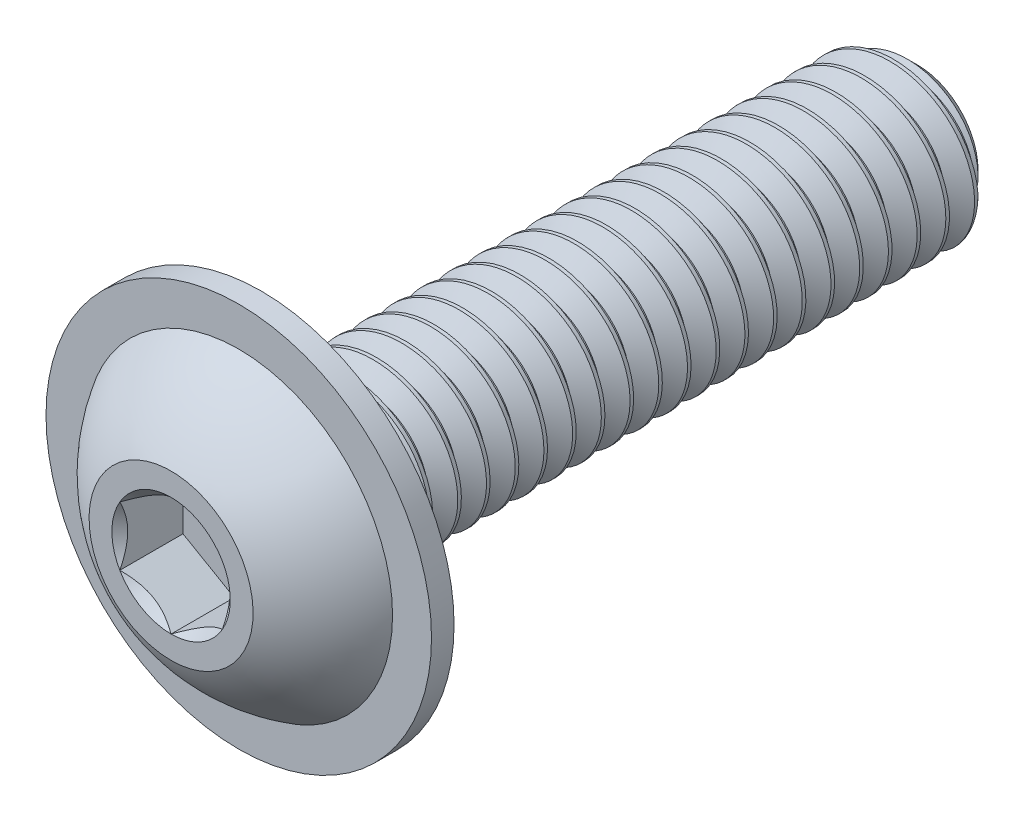
SolidWorks part; units mm, degrees
ref_plane "Front" through (0, 0, 0) normal (0, 0, 1) x (1, 0, 0)
ref_plane "Top" through (0, 0, 0) normal (0, 1, 0) x (1, 0, 0)
ref_plane "Right" through (0, 0, 0) normal (1, 0, 0) x (0, 0, -1)
sketch "Sketch1" plane through (0, 0, 0) normal (1, 0, 0) x (0, 0, -1)
  line L2 (2.2, 2) -> (18.2, 2)
  line L3 (18.2, 2) -> (18.2, 0)
  line L4 (18.2, 0) -> (2.2, 0)
  line L6 (1.65, 3.75) -> (2.2, 3.75) construction
  line L7 (18.2, 2) -> (18.2, -2) construction
  line L8 (0, 0) -> (2.2, 0) construction
  line L9 (2.2, 3.75) -> (2.2, -3.75) construction
  line L11 (2.2, 2) -> (2.2, 0)
  line L13 (0, 1.25) -> (0, -1.25) construction
  line L14 (0, 1.25) -> (0, 2) construction
  line L15 (1.65, 3.75) -> (1.65, 4.7) construction
  line L16 (1.65, 4.7) -> (2.2, 4.7) construction
  line L17 (2.2, 4.7) -> (2.2, 3.75) construction
  line L18 (2.2, 4.7) -> (2.2, -4.7) construction
  arc A3 (0, 2) -> (1.65, 3.75) centre (3.8742, 0) cw construction
  dimension "D1" = 0.55
revolve "Revolve1" add sketch "Sketch1" angle 360 mid plane about L4
sketch "Sketch3" plane through (0, 0, -18.2) normal (0, 0, -1) x (-1, 0, 0)
  circle A0 centre (0, 0) radius 2
curve "Helix/Spiral1" pitch 0.7 height 16.7 radius 2 centre (0, 0, -18.2) axis (0, 0, 1) start towards (0, 1, 0)
sketch "Sketch2" plane through (0, 0, 0) normal (1, 0, 0) x (0, 0, -1)
  line L0 (18.2, 2) -> (18.8125, 2)
  line L1 (18.8125, 2) -> (18.55, 1.5453)
  line L2 (18.55, 1.5453) -> (18.4625, 1.5453)
  line L3 (18.4625, 1.5453) -> (18.2, 2)
  line L4 (18.3313, 1.7727) -> (18.6812, 1.7727) construction
  dimension "D1" = 60
  dimension "D2" = 0.0875
  dimension "D3" = 0.35
chamfer "Chamfer1" distance 0.525 angle 45 1 edges at (0, 2, -18.2)
sweep "Cut-Sweep1" cut profiles "Sketch2" path "Helix/Spiral1" align with end faces yes
sketch "Sketch7" plane through (0, 0, 0) normal (1, 0, 0) x (0, 0, -1)
  line L6 (1.65, 3.75) -> (2.2, 3.75) construction
  line L8 (0, 0) -> (2.2, 0) construction
  line L11 (2.2, 3.75) -> (2.2, -3.75) construction
  line L12 (1.65, 3.75) -> (2.2, 3.75)
  line L13 (0, 0) -> (2.2, 0)
  line L14 (0, 1.25) -> (0, -1.25) construction
  line L15 (2.2, 3.75) -> (2.2, 0)
  line L16 (0, 2) -> (0, 0)
  arc A2 (1.65, 3.75) -> (0, 2) centre (3.8742, 0) ccw construction
  arc A3 (1.65, 3.75) -> (0, 2) centre (3.8742, 0) ccw
revolve "Revolve2" add sketch "Sketch7" angle 360 mid plane about L13
sketch "Sketch11" plane through (0, 0, -2.2) normal (0, 0, -1) x (-1, 0, 0)
  circle A0 centre (0, 0) radius 4.7
extrude "Boss-Extrude3" add sketch "Sketch11" against normal up to vertex (0.55 mm away) up to point (0, 3.75, -1.65)
sketch "Sketch5" plane through (0, 0, 0) normal (0, 0, 1) x (1, 0, 0)
  line L1 (1.25, -0.7217) -> (1.25, 0.7217)
  line L2 (1.25, 0.7217) -> (0, 1.4434)
  line L3 (0, 1.4434) -> (-1.25, 0.7217)
  line L4 (-1.25, 0.7217) -> (-1.25, -0.7217)
  line L5 (-1.25, -0.7217) -> (0, -1.4434)
  line L6 (0, -1.4434) -> (1.25, -0.7217)
  circle A0 centre (0, 0) radius 1.25 construction
extrude "Cut-Extrude2" cut sketch "Sketch5" against normal blind 1.54
sketch "Sketch6" plane through (0, 0, 0) normal (0, 0, 1) x (1, 0, 0)
  circle A0 centre (0, 0) radius 1.4434
extrude "Cut-Extrude3" cut sketch "Sketch6" against normal blind 1.54 draft 45
sketch "Sketch9" [suppressed] plane through (0, 0, -5.0546) normal (0, 0, 1) x (1, 0, 0)
  circle A2 centre (0, 0) radius 4.7625
extrude "Boss-Extrude2" [suppressed] add sketch "Sketch9" against normal offset from surface (6.35 mm away) 31.75 up to face at (0, 1.475, -18.2)
sketch "Sketch10" plane through (0, 0, 0) normal (1, 0, 0) x (0, 0, -1)
  line L0 (18.2, 2) -> (18.2, -2) construction
  point P0 (17.15, -2)
  dimension "D1" = 1.05
equation "\"D3@Helix/Spiral1\" = \"Lg@Sketch1\" + \"D4@Helix/Spiral1\""
equation "\"D2@Sketch2\" = \"D4@Helix/Spiral1\" * .125"
equation "\"D3@Sketch2\" = \"D4@Helix/Spiral1\" * .5"
equation "\"D1@Chamfer1\" = \"D4@Helix/Spiral1\" * .75"
equation "\"D1@Cut-Extrude2\" = \"Head Ht@Sketch1\" * .7"
equation "\"D1@Sketch1\" = \"Head Ht@Sketch1\" * .25"
equation "\"D1@Sketch10\" = \"D4@Helix/Spiral1\" * 1.5"
equation "\"D1@Cut-Extrude3\" = \"D1@Cut-Extrude2\""
